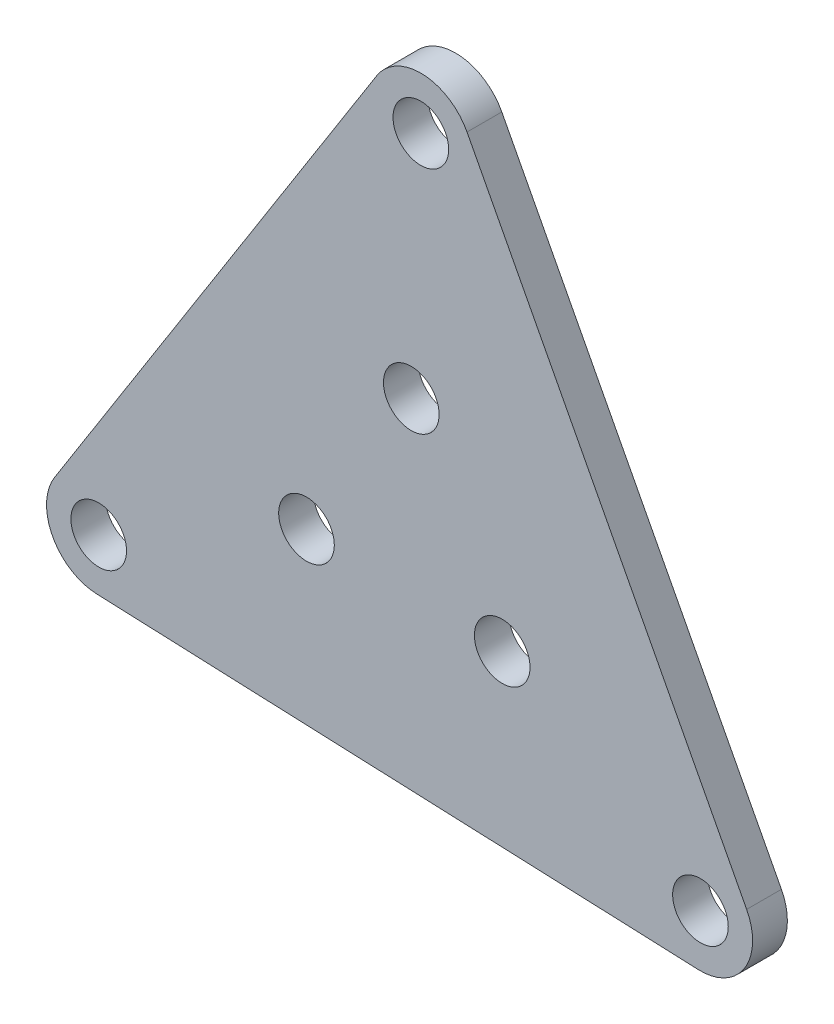
SolidWorks part; units mm, degrees
material "Thornel Mat VMA"
ref_plane "Front Plane" through (0, 0, 0) normal (0, 0, 1) x (1, 0, 0)
ref_plane "Top Plane" through (0, 0, 0) normal (0, 1, 0) x (1, 0, 0)
ref_plane "Right Plane" through (0, 0, 0) normal (1, 0, 0) x (0, 0, -1)
sketch "Sketch1" plane through (0, 0, 0) normal (0, 0, 1) x (1, 0, 0)
  line L3 (-17.8358, -12.2835) -> (16.7764, -13.6949)
  line L4 (19.5557, -9.3045) -> (3.4719, 21.3763)
  line L5 (-1.7199, 21.588) -> (-20.2484, -7.6813)
  line L6 (-17.8358, -12.2835) -> (16.7764, -13.6949)
  line L7 (19.5557, -9.3045) -> (3.4719, 21.3763)
  line L8 (-1.7199, 21.588) -> (-20.2484, -7.6813)
  line L11 (0.2651, 6.5) -> (-5.7617, -3.0204) construction
  line L12 (-5.7617, -3.0204) -> (5.4966, -3.4796) construction
  line L13 (5.4966, -3.4796) -> (0.2651, 6.5) construction
  circle A0 centre (16.8987, -10.6974) radius 1.6 construction
  circle A1 centre (-17.7136, -9.286) radius 1.6 construction
  circle A2 centre (0.8149, 19.9834) radius 1.6 construction
  arc A3 (16.7764, -13.6949) -> (19.5557, -9.3045) centre (16.8987, -10.6974) ccw
  arc A4 (3.4719, 21.3763) -> (-1.7199, 21.588) centre (0.8149, 19.9834) ccw
  arc A5 (-20.2484, -7.6813) -> (-17.8358, -12.2835) centre (-17.7136, -9.286) ccw
  arc A6 (16.7764, -13.6949) -> (19.5557, -9.3045) centre (16.8987, -10.6974) ccw
  arc A7 (3.4719, 21.3763) -> (-1.7199, 21.588) centre (0.8149, 19.9834) ccw
  arc A8 (-20.2484, -7.6813) -> (-17.8358, -12.2835) centre (-17.7136, -9.286) ccw
  circle A9 centre (16.8987, -10.6974) radius 1.6
  circle A10 centre (-17.7136, -9.286) radius 1.6
  circle A11 centre (0.8149, 19.9834) radius 1.6
  circle A16 centre (0, 0) radius 3.2527 construction
  circle A17 centre (0, 0) radius 9 construction
  circle A18 centre (0.2651, 6.5) radius 1.6
  circle A19 centre (-5.7617, -3.0204) radius 1.6
  circle A20 centre (5.4966, -3.4796) radius 1.6
  point P23 (0.2447, 6)
  dimension "D2" = 18
  dimension "D3" = 3.2
  dimension "D4" = 6.5
  dimension "D1" = 0
extrude "Boss-Extrude1" add sketch "Sketch1" along normal blind 2
